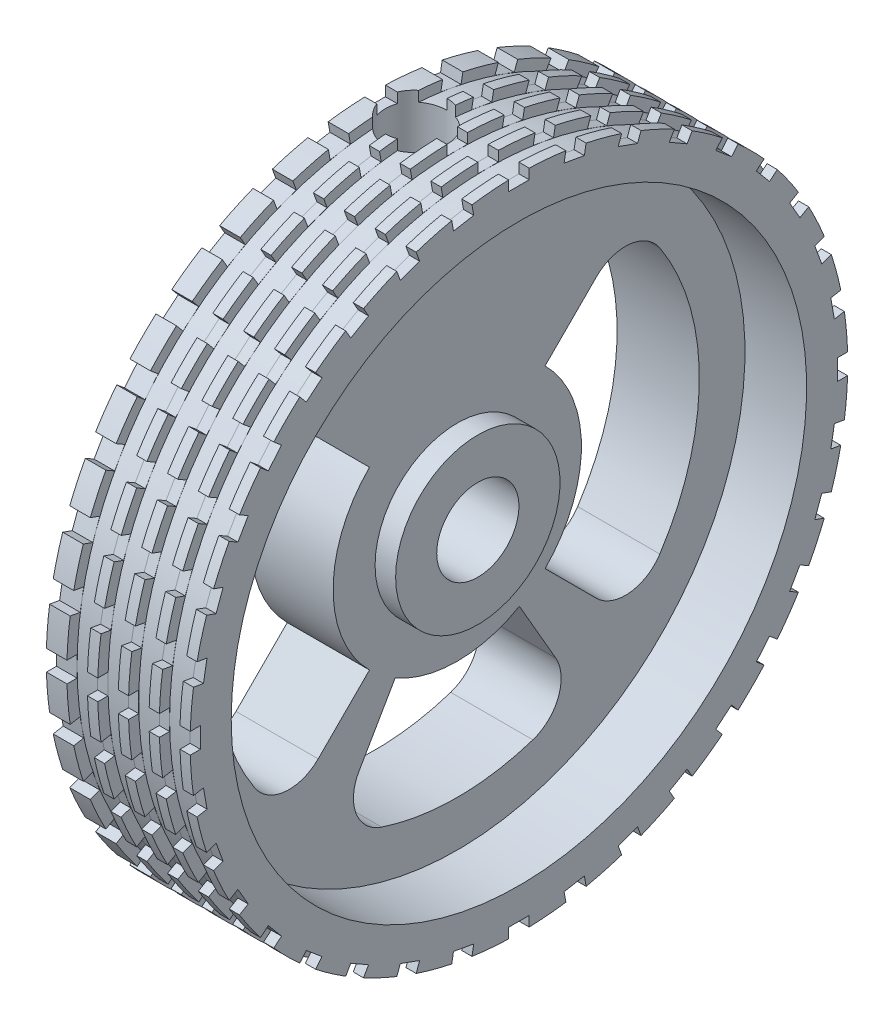
SolidWorks part; units mm, degrees
ref_plane "Front Plane" through (0, 0, 0) normal (0, 0, 1) x (1, 0, 0)
ref_plane "Top Plane" through (0, 0, 0) normal (0, 1, 0) x (1, 0, 0)
ref_plane "Right Plane" through (0, 0, 0) normal (1, 0, 0) x (0, 0, -1)
sketch "Sketch1" plane through (0, 0, 0) normal (0, 0, 1) x (1, 0, 0)
  line L0 (0, 0) -> (11.194, 0) construction
  line L1 (0, 2) -> (5, 2)
  line L2 (0, 2) -> (0, 16)
  line L3 (0, 16) -> (7, 16)
  line L4 (5, 2) -> (5, 4)
  line L5 (5, 4) -> (4, 4)
  line L6 (4, 4) -> (4, 14)
  line L7 (4, 14) -> (7, 14)
  line L8 (7, 14) -> (7, 16)
  point P5 (5.5, 14)
  dimension "D1" = 5
  dimension "D2" = 7
  dimension "D3" = 4
  dimension "D4" = 8
  dimension "D5" = 4
  dimension "D6" = 28
  dimension "D7" = 32
revolve "Revolve1" add sketch "Sketch1" angle 360 about L0
sketch "Sketch3" plane through (0, 0, 0) normal (0, 0, 1) x (1, 0, 0)
  line L0 (0, 0) -> (7.5349, 0) construction
  line L1 (2, 0) -> (2, 16)
  line L2 (7, 16) -> (0, 16) construction
  line L3 (2, 16) -> (3.5, 16)
  line L4 (3.5, 16) -> (3.5, 11.5)
  line L5 (3.5, 11.5) -> (2.9, 11.5)
  line L6 (2.9, 11.5) -> (2.9, 0)
  line L7 (2.9, 0) -> (2, 0)
  line L8 (2, 16) -> (2, 0) construction
  line L9 (2, 0) -> (2, 22.7436) construction
  dimension "D1" = 2
  dimension "D2" = 4.5
  dimension "D3" = 3
  dimension "D4" = 1.8
revolve "Cut-Revolve1" cut sketch "Sketch3" angle 360 about L9
sketch "Sketch4" plane through (0, 0, 0) normal (1, 0, 0) x (0, 0, -1)
  line L0 (0, 11.7788) -> (0, -11.7788) construction
  line L1 (-3.0209, 5.2323) -> (-5.8894, 10.2007)
  line L2 (3.0209, 5.2323) -> (5.8894, 10.2007)
  line L3 (0, 0) -> (14, 0) construction
  line L4 (14, 0) -> (-11.7788, 0) construction
  line L5 (3.0209, -5.2323) -> (5.8894, -10.2007)
  line L6 (-3.0209, -5.2323) -> (-5.8894, -10.2007)
  line L7 (-8.3289, -8.3289) -> (-4.2722, -4.2722)
  line L8 (-8.3289, 8.3289) -> (-4.2722, 4.2722)
  line L9 (8.3289, -8.3289) -> (4.2722, -4.2722)
  line L10 (8.3289, 8.3289) -> (4.2722, 4.2722)
  circle A0 centre (0, 0) radius 6.0418
  circle A1 centre (0, 0) radius 11.7788
  circle A2 centre (0, 0) radius 14 construction
  dimension "D1" = 30
  dimension "D2" = 45
extrude "Cut-Extrude4" cut sketch "Sketch4" along direction (-1, 0, 0) on the side of the normal through all contours L9 A1 L10 A0 | L6 A1 L5 A0 | L8 A1 L7 A0 region at (0, 0, 8.2992) region at (0, 0, -8.2992) region at (0, -8.8026, 0)
sketch "Sketch6" plane through (0, 0, 0) normal (0, 1, 0) x (1, 0, 0)
  line L9 (0, 0) -> (7, 0) construction
  line L13 (5.5, 16) -> (5.5, 15.5)
  line L16 (7, -16) -> (7, 16) construction
  line L17 (5.5, 16) -> (6.5, 16)
  line L18 (7, 16) -> (0, 16) construction
  line L19 (6.5, 16) -> (6.5, 15.5)
  line L20 (6.5, 15.5) -> (5.5, 15.5)
  dimension "D1" = 0.5
  dimension "D2" = 0.5
  dimension "D3" = 1
revolve "Cut-Revolve2" cut sketch "Sketch6" angle 360 about L9
sketch "Sketch7" plane through (0, 0, 0) normal (0, 1, 0) x (1, 0, 0)
  line L0 (7, -14) -> (7, 14) construction
  line L1 (0, 0.5) -> (7, 0.5)
  line L2 (0, 0.5) -> (0, -0.5)
  line L3 (0, -0.5) -> (7, -0.5)
  line L4 (7, 0.5) -> (7, -0.5)
  point P7 (0, 0)
  dimension "D1" = 1
extrude "Cut-Extrude5" cut sketch "Sketch7" along normal blind 20 from offset 15.5
pattern_circular "CirPattern1" count 36 over 360 about axis through (0, 0, 0) along (-1, 0, 0) of "Cut-Extrude5"
pattern_linear "LPattern1" count 4 spacing 1.5 along (-1, 0, 0) of "Cut-Revolve2"
fillet "Fillet1" radius 2 1 edges at (2, 8.3289, 8.3289)
fillet "Fillet2" radius 2 1 edges at (2, -8.3289, 8.3289)
fillet "Fillet3" radius 2 1 edges at (2, -10.2007, 5.8894)
fillet "Fillet4" radius 2 1 edges at (2, -10.2007, -5.8894)
fillet "Fillet5" radius 2 1 edges at (2, -8.3289, -8.3289)
fillet "Fillet6" radius 2 1 edges at (2, 8.3289, -8.3289)
